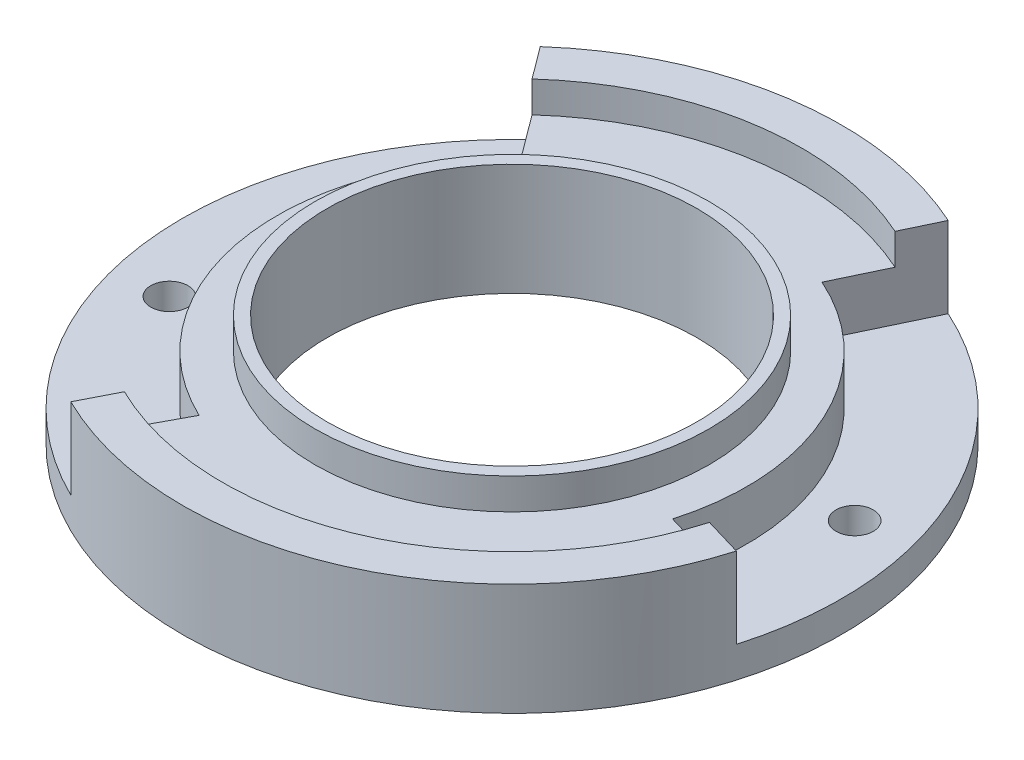
SolidWorks part; units mm, degrees
ref_plane "Plan de face" through (0, 0, 0) normal (0, 0, 1) x (1, 0, 0)
ref_plane "Plan de dessus" through (0, 0, 0) normal (0, 1, 0) x (1, 0, 0)
ref_plane "Plan de droite" through (0, 0, 0) normal (1, 0, 0) x (0, 0, -1)
sketch "Esquisse1" plane through (0, 0, 0) normal (0, 1, 0) x (1, 0, 0)
  circle A2 centre (0, 0) radius 26.5068
  circle A3 centre (0, 0) radius 14.875
  dimension "D3" = 29.75
extrude "Boss.-Extru.1" add sketch "Esquisse1" against normal blind 5 contours A3 | A2
sketch "Esquisse2" plane through (0, 0, 0) normal (0, 1, 0) x (1, 0, 0)
  circle A0 centre (0, 0) radius 15.85
  circle A1 centre (0, 0) radius 23.3
extrude "Enlèv. mat.-Extru.1" cut sketch "Esquisse2" against normal blind 2.5
sketch "Esquisse3" plane through (0, -2.5, 0) normal (0, 1, 0) x (1, 0, 0)
  ellipse E0 centre (0.0114, -22.1505) end of major axis (9.3627, -22.053) minor radius 5.5623
extrude "Enlèv. mat.-Extru.2" [suppressed] cut sketch "Esquisse3" against normal through all and the other way blind 94
sketch "Esquisse5" [suppressed] plane through (0, 0, 0) normal (0, 1, 0) x (1, 0, 0)
  circle A0 centre (-10.5276, 6.2256) radius 2.5
  circle A1 centre (-10.5276, -6.2744) radius 2.5
  circle A2 centre (10.4724, -6.2744) radius 2.5
  circle A3 centre (10.4724, 6.2256) radius 2.5
extrude "Enlèv. mat.-Extru.3" [suppressed] cut sketch "Esquisse5" against normal through all
sketch "Sketch1" plane through (0, -5, 0) normal (0, -1, 0) x (1, 0, 0)
  circle A0 centre (0, 0) radius 26.5068
  circle A1 centre (0, 0) radius 26.5068 construction
extrude "Boss-Extrude1" add sketch "Sketch1" along normal blind 50
sketch "Sketch4" plane through (0, -5, 0) normal (0, 1, 0) x (1, 0, 0)
  circle A0 centre (-10.4996, -4.3179) radius 2.5
  circle A1 centre (10.5004, -4.3179) radius 2.5
  circle A2 centre (-10.4996, 8.1821) radius 2.5
  circle A3 centre (10.5004, 8.1821) radius 2.5
  circle A4 centre (-10.4996, -4.3179) radius 1
  circle A5 centre (10.5004, -4.3179) radius 1.025
  circle A6 centre (10.5004, 8.1821) radius 1.025
  circle A7 centre (-10.4996, 8.1821) radius 1.025
  dimension "D1" = 5
  dimension "D2" = 5
  dimension "D3" = 5
  dimension "D4" = 5
  dimension "D8" = 2
  dimension "D9" = 2.05
  dimension "D10" = 2.05
  dimension "D11" = 2.05
  dimension "D5" = 21
  dimension "D6" = 21
  dimension "D7" = 12.5
  dimension "D12" = 21
  dimension "D13" = 12.5
extrude "Boss.-Extru.2" [suppressed] add sketch "Sketch4" along normal blind 15
sketch "Sketch6" plane through (0, -2.5, 0) normal (0, 1, 0) x (1, 0, 0)
  line L1 (-2.3918, -18.5524) -> (-0.3918, -18.5524)
  line L2 (-2.3918, -18.5524) -> (-2.3918, -27.3139)
  line L3 (-2.3918, -27.3139) -> (-0.3918, -27.3139)
  line L4 (-0.3918, -18.5524) -> (-0.3918, -27.3139)
  line L9 (18.0384, -1.449) -> (28.4147, -1.449)
  line L10 (18.0384, -1.449) -> (18.0384, 0)
  line L11 (18.0384, 0) -> (28.4147, 0)
  line L12 (28.4147, -1.449) -> (28.4147, 0)
  dimension "D1" = 2
extrude "Cut-Extrude2" [suppressed] cut sketch "Sketch6" against normal blind 2 and the other way blind 6
sketch "Sketch8" plane through (0, -5, 0) normal (0, 1, 0) x (1, 0, 0)
  line L1 (-9.3177, -9.6114) -> (9.3627, -9.6114)
  line L2 (-9.3177, -9.6114) -> (-9.3177, -26.872)
  line L3 (-9.3177, -26.872) -> (9.3627, -26.872)
  line L4 (9.3627, -9.6114) -> (9.3627, -26.872)
extrude "Cut-Extrude3" [suppressed] cut sketch "Sketch8" against normal blind 2
sketch "Sketch9" plane through (0, -2.5, 0) normal (0, 1, 0) x (1, 0, 0)
  line L0 (4.0426, -18.2947) -> (5.6292, -25.9022)
  line L1 (4.0426, -18.2947) -> (6.0005, -17.8863)
  line L2 (6.0005, -17.8863) -> (7.5682, -25.4034)
  line L3 (7.5682, -25.4034) -> (5.6292, -25.9022)
  circle A0 centre (0, 0) radius 26.5068 construction
  dimension "D1" = 2
extrude "Cut-Extrude5" [suppressed] cut sketch "Sketch9" against normal blind 2 and the other way blind 4
sketch "Sketch10" plane through (0, -55, 0) normal (0, -1, 0) x (1, 0, 0)
  circle A0 centre (0, 0) radius 26.5068
extrude "Cut-Extrude6" cut sketch "Sketch10" against normal blind 46
sketch "Sketch11" plane through (0, -2.5, 0) normal (0, 1, 0) x (1, 0, 0)
  line L0 (-6.883, -14.3021) -> (-12.2218, -24.7789)
  line L1 (-11.1053, 11.1453) -> (-18.357, 20.9008)
  line L2 (6.2757, 14.3502) -> (11.7235, 25.7863)
  line L3 (15.1368, -4.3435) -> (27.23, -7.9355)
  circle A0 centre (-0.047, -0.0938) radius 15.7672
  arc A1 (-18.357, 20.9008) -> (-12.2218, -24.7789) centre (0.4462, 0.1744) ccw
  arc A3 (27.23, -7.9355) -> (11.7235, 25.7863) centre (0.4462, 0.1744) ccw
  arc A4 (15.1368, -4.3435) -> (6.2757, 14.3502) centre (1.6624, 0.7164) ccw
  arc A6 (-6.883, -14.3021) -> (-11.1053, 11.1453) centre (-0.047, -0.0938) cw
  circle M4 centre (0, 0) radius 15.85
  circle M5 centre (0, 0) radius 23.3
extrude "Cut-Extrude7" cut sketch "Sketch11" along normal blind 23 contours L1 L0 M4 M5 | A0 M5 M4 | A4 L3 L2 M4 M5 | M5 | L1 A1 L0 M5 | L3 A3 L2 M5 region at (7.0721, -2.5, 15.9005) region at (-16.6856, -2.5, 2.5212) region at (-11.6741, -2.5, 22.6284) region at (21.6401, -2.5, -9.9304) region at (16.5139, -2.5, -7.6886)
sketch "Sketch12" plane through (0, -2.5, 0) normal (0, 1, 0) x (1, 0, 0)
  line L0 (-17.5723, 19.8451) -> (-13.0056, 13.7018)
  line L1 (10.9409, 24.1435) -> (7.665, 17.2665)
  line L2 (-8.1085, -17.0627) -> (-11.7123, -23.7789)
  line L3 (18.1505, -5.2387) -> (25.4509, -7.4071)
  line L4 (-15.6512, 17.2607) -> (-17.5723, 19.8451) construction
  line L5 (9.5615, 21.2478) -> (10.9409, 24.1435) construction
  line L6 (22.3767, -6.494) -> (25.4509, -7.4071) construction
  arc A0 (-13.0056, 13.7018) -> (-8.1085, -17.0627) centre (0, 0) ccw
  arc A1 (-17.5723, 19.8451) -> (-11.7123, -23.7789) centre (0, 0) ccw
  arc A2 (25.4509, -7.4071) -> (10.9409, 24.1435) centre (0, 0) ccw construction
  arc A3 (-10.2561, -20.9213) -> (22.3767, -6.494) centre (0, 0) ccw construction
  arc A4 (18.1505, -5.2387) -> (7.665, 17.2665) centre (0, 0) ccw
  arc A5 (25.4509, -7.4071) -> (10.9409, 24.1435) centre (0, 0) ccw
  arc A8 (-11.7123, -23.7789) -> (25.4509, -7.4071) centre (0, 0) ccw construction
extrude "Cut-Extrude8" cut sketch "Sketch12" against normal blind 4
sketch "Esquisse6" plane through (0, -2.5, 0) normal (0, 1, 0) x (1, 0, 0)
  line L0 (-11.7123, -23.7789) -> (-10.2561, -20.9213)
  line L1 (-11.7123, -23.7789) -> (-10.1952, -20.9516)
  line L2 (-11.7123, -23.7789) -> (-8.1085, -17.0627) construction
  arc A0 (-10.1952, -20.9516) -> (-10.2561, -20.9213) centre (6.7209, 13.2066) ccw
extrude "Boss.-Extru.3" [suppressed] add sketch "Esquisse6" along normal up to vertex
sketch "Sketch13" plane through (0, -5, 0) normal (0, 1, 0) x (1, 0, 0)
  circle A0 centre (0, 0) radius 14.875
extrude "Cut-Extrude9" cut sketch "Sketch13" against normal blind 10
sketch "Sketch14" [suppressed] plane through (0, -2.5, 0) normal (0, 1, 0) x (1, 0, 0)
  circle A0 centre (0, 0) radius 25
  arc A2 (25.4509, -7.4071) -> (10.9409, 24.1435) centre (0, 0) ccw construction
  circle A3 centre (0, 0) radius 26.5068
  arc A4 (-17.5723, 19.8451) -> (-11.7123, -23.7789) centre (0, 0) ccw construction
  dimension "D1" = 50
sketch "Sketch17" plane through (0, -6.5, 0) normal (0, 1, 0) x (1, 0, 0)
  line L0 (-21.5892, -5.972) -> (21.5892, 5.972) construction
  point P0 (-21.5892, -5.972)
  point P2 (21.5892, 5.972)
  dimension "D1" = 44.8
hole_wizard "Trous de centrage Ø3.0mm1" positions "Sketch17" profile "Sketch16" hole size "Ø3.0" standard "ISO" end condition through all
sketch "Sketch16" plane through (-21.5892, -6.5, 5.972) normal (1, 0, 0) x (0, 0, 1)
  line L0 (0, 0) -> (0, 2.5)
  line L1 (0, 2.5) -> (1.5, 2.5)
  line L2 (1.5, 2.5) -> (1.5, 0)
  line L5 (1.5, 0) -> (0, 0)
  line L11 (0, -6.35) -> (0, 107.95) construction
  dimension "Thru Hole Dia." = 3
  dimension "Thru Hole Depth" = 2.5
